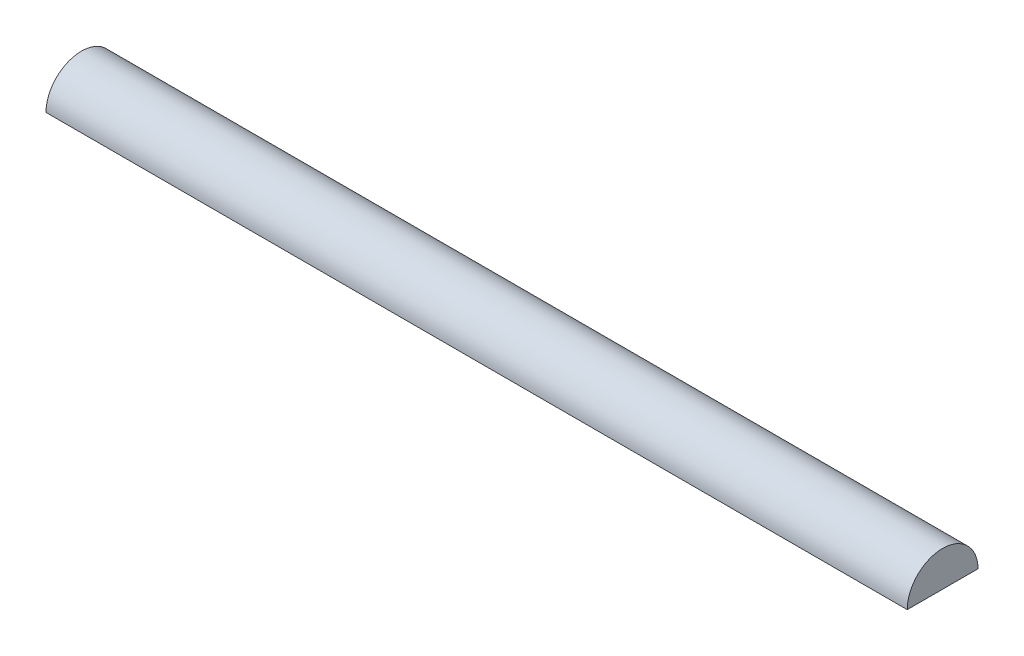
SolidWorks part; units mm, degrees
ref_plane "Front Plane" through (0, 0, 0) normal (0, 0, 1) x (1, 0, 0)
ref_plane "Top Plane" through (0, 0, 0) normal (0, 1, 0) x (1, 0, 0)
ref_plane "Right Plane" through (0, 0, 0) normal (1, 0, 0) x (0, 0, -1)
sketch "Sketch1" plane through (0, 0, 0) normal (0, 1, 0) x (-1, 0, 0)
  line L0 (3855.7016, 1120) -> (1793.3847, 337.92)
  line L1 (1793.3847, 337.92) -> (3247.5197, 368.69)
  line L2 (3247.5197, 368.69) -> (3247.5197, 0)
  line L3 (3247.5197, 0) -> (8763.0034, 0)
  line L4 (8763.0034, 0) -> (8763.0034, 1070)
  line L5 (9493.3879, 1120) -> (9793.3847, 1070)
  line L6 (9793.3847, 1070) -> (8763.0034, 1070)
  line L7 (9493.3879, 1120) -> (3855.7016, 1120)
  dimension "D1" = 368.69
  dimension "D2" = 1070
  dimension "D3" = 8000
  dimension "D4" = 50
  dimension "D5" = 337.92
revolve "Revolve1" add sketch "Sketch1" angle 360 about L3
sketch "Sketch2" plane through (0, 0, 0) normal (1, 0, 0) x (0, 0, -1)
  circle A0 centre (0, 0) radius 1232.8576
extrude "Boss-Extrude1" add sketch "Sketch2" along normal blind 10000 and the other way blind 20000 separate body
combine bodies "Combine1" operation type subtract main body 102 bodies to subtract 101
sketch "Sketch3" plane through (0, 0, 0) normal (0, 1, 0) x (-1, 0, 0)
  line L0 (20000, -1232.8576) -> (20000, 1232.8576) construction
  line L1 (-10000, 2080.3524) -> (20000, 2080.3524)
  line L2 (-10000, 2080.3524) -> (-10000, -1559.5909)
  line L3 (-10000, -1559.5909) -> (20000, -1559.5909)
  line L4 (20000, 2080.3524) -> (20000, -1559.5909)
  line L5 (-10000, 1232.8576) -> (-10000, -1232.8576) construction
extrude "Cut-Extrude1" cut sketch "Sketch3" against normal through all
